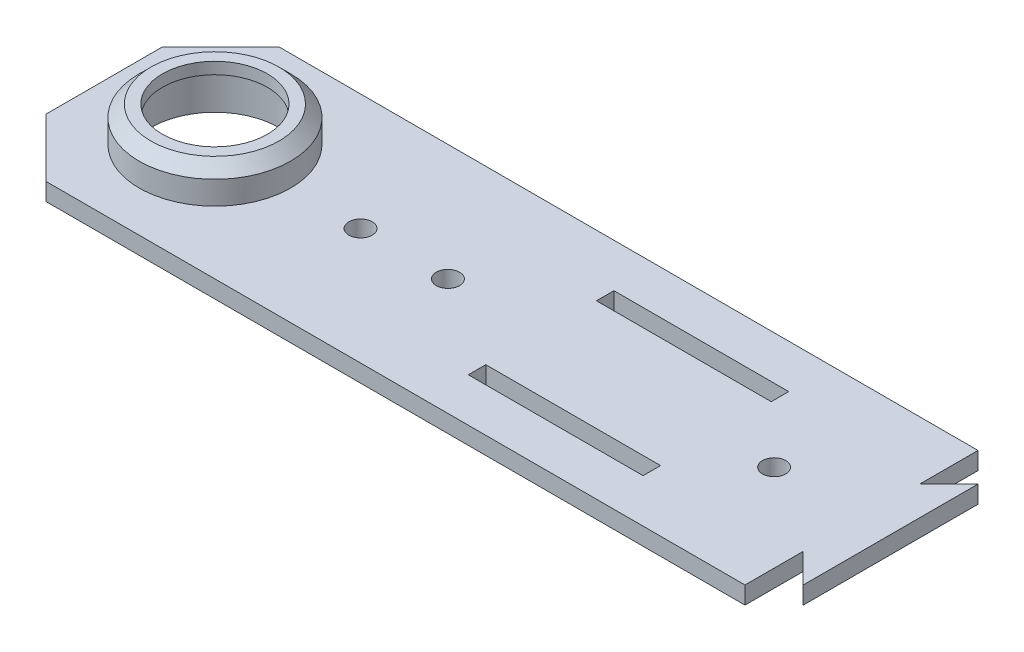
SolidWorks part; units mm, degrees
ref_plane "Alzado" through (0, 0, 0) normal (0, 0, 1) x (1, 0, 0)
ref_plane "Planta" through (0, 0, 0) normal (0, 1, 0) x (1, 0, 0)
ref_plane "Vista lateral" through (0, 0, 0) normal (1, 0, 0) x (0, 0, -1)
sketch "Croquis1" plane through (0, 0, 0) normal (0, 1, 0) x (1, 0, 0)
  line L0 (65, 10) -> (70, 15)
  line L1 (-65, -20) -> (65, -20)
  line L2 (-65, -20) -> (-65, 20)
  line L3 (-65, 20) -> (65, 20)
  line L4 (65, -20) -> (65, -10)
  line L5 (-65, -20) -> (65, 20) construction
  line L6 (-65, 20) -> (65, -20) construction
  line L7 (70, 15) -> (70, -15)
  line L8 (70, -15) -> (65, -10)
  line L9 (65, 10) -> (65, 20)
  line L10 (0, 0) -> (77.1384, 0) construction
  line L12 (10, 9.5) -> (40, 9.5)
  line L13 (10, 9.5) -> (10, 12.5)
  line L14 (10, 12.5) -> (40, 12.5)
  line L15 (40, 9.5) -> (40, 12.5)
  line L16 (10, 9.5) -> (40, 12.5) construction
  line L17 (10, 12.5) -> (40, 9.5) construction
  line L18 (10, -12.5) -> (40, -12.5)
  line L19 (10, -12.5) -> (10, -9.5)
  line L20 (10, -9.5) -> (40, -9.5)
  line L21 (40, -12.5) -> (40, -9.5)
  line L22 (10, -12.5) -> (40, -9.5) construction
  line L23 (10, -9.5) -> (40, -12.5) construction
  circle A2 centre (-46, 0) radius 11
  circle A3 centre (-46, 0) radius 12.5 construction
  circle A4 centre (-21, 0) radius 2
  circle A5 centre (-6, 0) radius 2
  circle A6 centre (50, 0) radius 2
  point P0 (0, 0)
  point P8 (70, 0)
  point P19 (25, 11)
  point P35 (25, -11)
  dimension "D7" = 19
  dimension "D8" = 22
  dimension "D12" = 25
  dimension "D13" = 4
  dimension "D14" = 4
  dimension "D17" = 4
  dimension "D1" = 130
  dimension "D2" = 45
  dimension "D3" = 45
  dimension "D4" = 20
  dimension "D5" = 30
  dimension "D6" = 40
  dimension "D9" = 3
  dimension "D10" = 30
  dimension "D11" = 40
  dimension "D15" = 15
  dimension "D16" = 10
  dimension "D18" = 12.5
  dimension "D19" = 12.5
  dimension "D20" = 25
extrude "Saliente-Extruir1" add sketch "Croquis1" along normal blind 3
sketch "Croquis2" plane through (0, 3, 0) normal (0, 1, 0) x (1, 0, 0)
  circle A0 centre (-46, 0) radius 11
  circle A1 centre (-46, 0) radius 13
  dimension "D1" = 2
extrude "Saliente-Extruir2" add sketch "Croquis2" along normal blind 4
sketch "Croquis3" plane through (0, 7, 0) normal (0, 1, 0) x (1, 0, 0)
  circle A0 centre (-46, 0) radius 13
  circle A1 centre (-46, 0) radius 9
  dimension "D1" = 18
extrude "Saliente-Extruir3" add sketch "Croquis3" along normal blind 2
chamfer "Chaflán1" distance 2 angle 45 1 edges at (-46, 9, 13)
chamfer "Chaflán2" distance 10 angle 45 2 edges at (-65, 1.5, 20) (-65, 1.5, -20)
